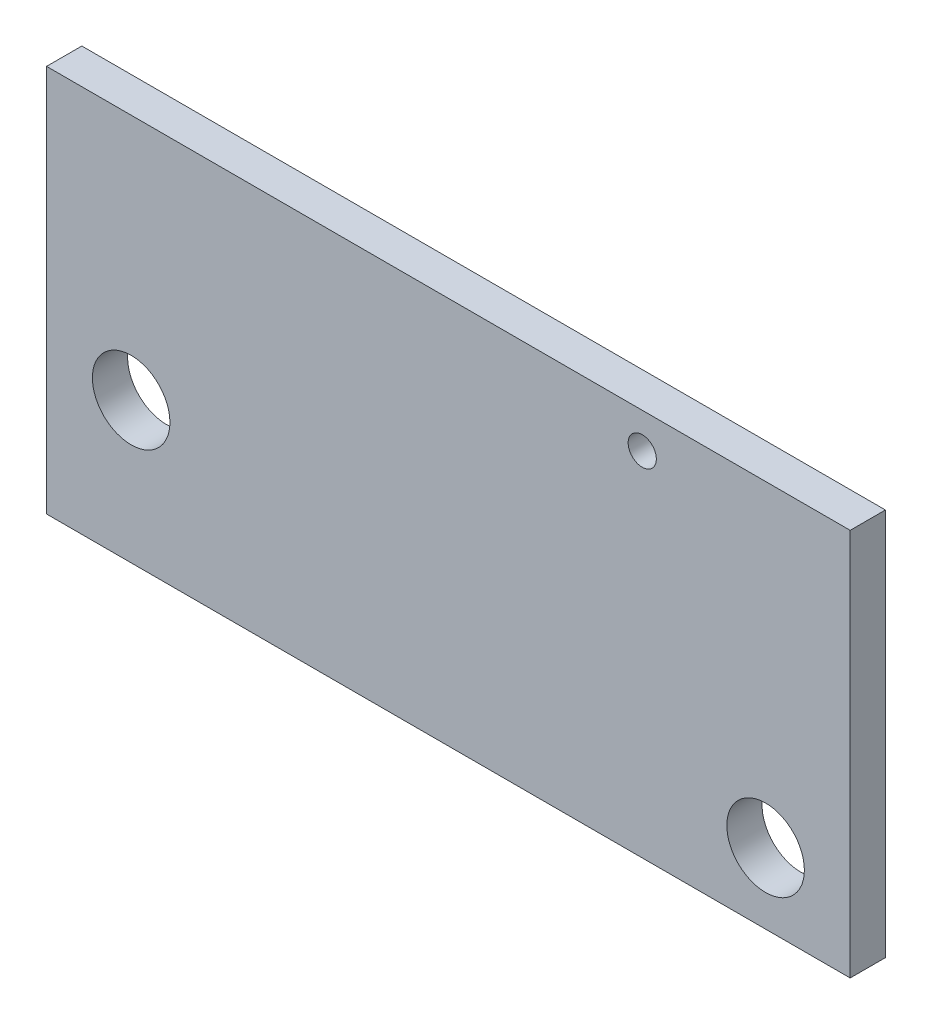
SolidWorks part; units mm, degrees
ref_plane "Front Plane" through (0, 0, 0) normal (0, 0, 1) x (1, 0, 0)
ref_plane "Top Plane" through (0, 0, 0) normal (0, 1, 0) x (1, 0, 0)
ref_plane "Right Plane" through (0, 0, 0) normal (1, 0, 0) x (0, 0, -1)
sketch "Sketch1" plane through (0, 0, 0) normal (0, 0, 1) x (1, 0, 0)
  line L1 (0, 0) -> (228, 0)
  line L2 (0, 0) -> (0, 110)
  line L3 (0, 110) -> (228, 110)
  line L4 (228, 0) -> (228, 110)
  circle A0 centre (24, 40) radius 11
  circle A1 centre (204, 20) radius 11
  circle A2 centre (169, 100) radius 4
  dimension "D3" = 22
  dimension "D8" = 8
  dimension "D1" = 228
  dimension "D2" = 110
  dimension "D4" = 24
  dimension "D5" = 40
  dimension "D6" = 24
  dimension "D7" = 20
  dimension "D9" = 10
  dimension "D10" = 59
extrude "Boss-Extrude1" add sketch "Sketch1" along normal blind 10
